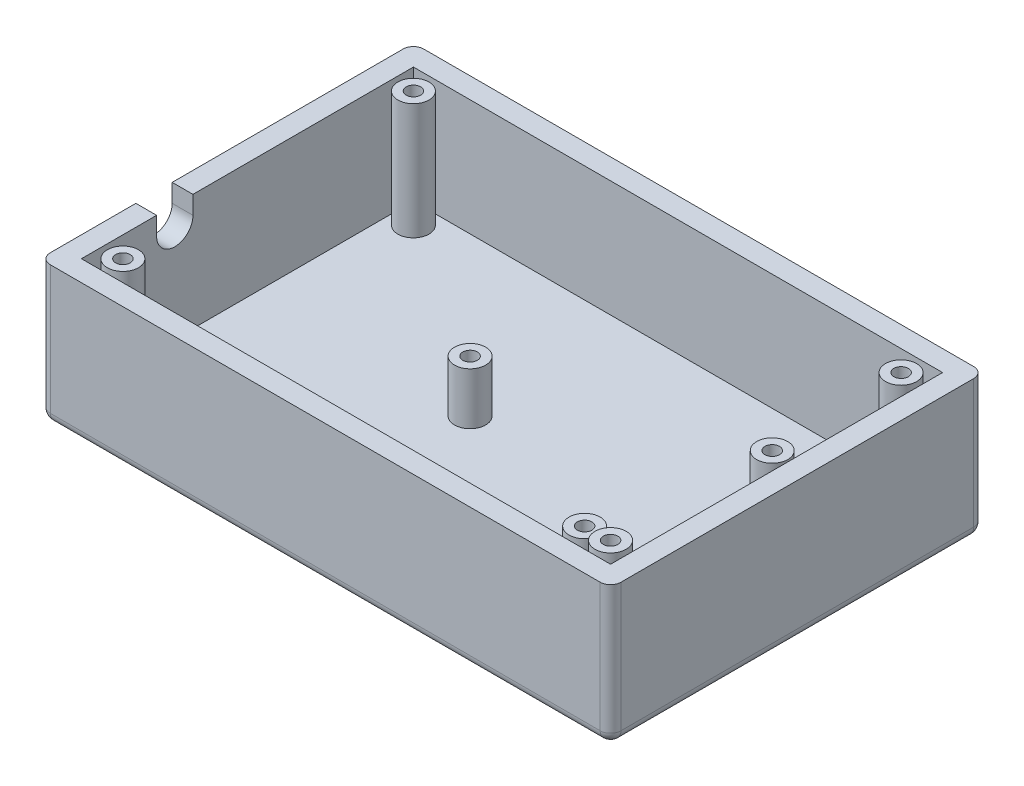
SolidWorks part; units mm, degrees
ref_plane "Front Plane" through (0, 0, 0) normal (0, 0, 1) x (1, 0, 0)
ref_plane "Top Plane" through (0, 0, 0) normal (0, 1, 0) x (1, 0, 0)
ref_plane "Right Plane" through (0, 0, 0) normal (1, 0, 0) x (0, 0, -1)
sketch "Sketch2" plane through (0, 0, 0) normal (0, 1, 0) x (1, 0, 0)
  line L1 (0, 0) -> (69.85, 0)
  line L2 (0, 0) -> (0, 45.72)
  line L3 (0, 45.72) -> (69.85, 45.72)
  line L4 (69.85, 0) -> (69.85, 45.72)
  dimension "D1" = 45.72
  dimension "D2" = 69.85
extrude "Boss-Extrude1" add sketch "Sketch2" along normal blind 17.018
sketch "Sketch3" plane through (0, 17.018, 0) normal (0, 1, 0) x (1, 0, 0)
  line L1 (2.54, 43.18) -> (67.31, 43.18)
  line L2 (2.54, 43.18) -> (2.54, 2.54)
  line L3 (2.54, 2.54) -> (67.31, 2.54)
  line L4 (67.31, 43.18) -> (67.31, 2.54)
  line L5 (0, 45.72) -> (0, 0) construction
  line L6 (69.85, 45.72) -> (0, 45.72) construction
  line L7 (69.85, 0) -> (69.85, 45.72) construction
  line L8 (0, 0) -> (69.85, 0) construction
  dimension "D1" = 2.54
  dimension "D2" = 2.54
  dimension "D3" = 2.54
  dimension "D4" = 2.54
  dimension "D5" = 40.64
extrude "Cut-Extrude1" cut sketch "Sketch3" against normal blind 14.224
sketch "Sketch9" plane through (0, 2.794, 0) normal (0, 1, 0) x (1, 0, 0)
  line L0 (67.31, 43.18) -> (67.31, 35.56)
  line L1 (67.31, 2.54) -> (67.31, 43.18) construction
  line L2 (67.31, 43.18) -> (66.675, 43.18)
  line L3 (67.31, 43.18) -> (2.54, 43.18) construction
  line L4 (66.675, 43.18) -> (66.675, 35.56)
  line L5 (66.675, 35.56) -> (67.31, 35.56)
  dimension "D1" = 7.62
  dimension "D2" = 0.635
sketch "Sketch13" plane through (0, 2.794, 0) normal (0, 1, 0) x (1, 0, 0)
  circle A0 centre (57.277, 32.3596) radius 1.905
  circle A1 centre (53.7972, 12.8778) radius 1.905
  circle A2 centre (28.7782, 23.876) radius 1.905
  dimension "D1" = 3.81
  dimension "D2" = 3.81
  dimension "D3" = 3.81
  dimension "D4" = 3.2004
  dimension "D5" = 9.398
  dimension "D6" = 19.4818
  dimension "D7" = 3.4798
  dimension "D8" = 8.4836
  dimension "D9" = 28.4988
extrude "Boss-Extrude5" add sketch "Sketch13" along normal blind 6.35
sketch "Sketch14" plane through (0, 9.144, 0) normal (0, 1, 0) x (1, 0, 0)
  circle A0 centre (57.277, 32.3596) radius 0.889
  circle A1 centre (53.7972, 12.8778) radius 0.889
  circle A2 centre (28.7782, 23.876) radius 0.889
  dimension "D2" = 1.778
extrude "Cut-Extrude4" cut sketch "Sketch14" against normal up to surface (6.35 mm away) up to face at (28.7782, 2.794, -21.971)
sketch "Sketch17" plane through (0, 0, 0) normal (-1, 0, 0) x (0, 0, 1)
  line L0 (-45.72, 17.018) -> (0, 17.018) construction
  line L1 (-45.72, 17.018) -> (-45.72, 0) construction
  line L2 (-16.1925, 14.7955) -> (-16.1925, 17.018)
  line L3 (-11.7475, 14.7955) -> (-11.7475, 17.018)
  line L4 (-11.7475, 17.018) -> (-16.1925, 17.018)
  arc A0 (-16.1925, 14.7955) -> (-11.7475, 14.7955) centre (-13.97, 14.7955) ccw
  dimension "D1" = 4.445
  dimension "D2" = 31.75
extrude "Cut-Extrude5" cut sketch "Sketch17" against normal up to surface (2.54 mm away) up to face at (2.54, 9.906, -22.86)
fillet "Fillet1" radius 1.27 8 edges at (34.925, 0, 0) (69.85, 0, -22.86) (34.925, 0, -45.72) (0, 0, -22.86) (0, 8.509, -45.72) (0, 8.509, 0) (69.85, 8.509, -45.72) (69.85, 8.509, 0)
sketch "Sketch18" plane through (0, 2.794, 0) normal (0, 1, 0) x (1, 0, 0)
  line L0 (2.54, 43.18) -> (2.54, 16.1925) construction
  line L1 (67.31, 2.54) -> (67.31, 43.18) construction
  line L5 (67.31, 43.18) -> (2.54, 43.18) construction
  line L7 (2.54, 2.54) -> (67.31, 2.54) construction
  line L8 (2.54, 2.54) -> (67.31, 2.54) construction
  line L9 (2.54, 43.18) -> (2.54, 2.54) construction
  line L10 (67.31, 43.18) -> (2.54, 43.18) construction
  line L11 (67.31, 2.54) -> (67.31, 43.18) construction
  circle A0 centre (5.08, 40.64) radius 1.905
  circle A1 centre (64.77, 40.64) radius 1.905
  circle A2 centre (5.08, 5.08) radius 1.905
  circle A3 centre (64.77, 5.08) radius 1.905
  dimension "D1" = 3.81
  dimension "D2" = 3.81
  dimension "D3" = 3.81
  dimension "D4" = 3.81
  dimension "D5" = 2.54
  dimension "D6" = 2.54
  dimension "D7" = 2.54
  dimension "D8" = 2.54
  dimension "D9" = 2.54
  dimension "D10" = 2.54
  dimension "D11" = 2.54
  dimension "D12" = 2.54
extrude "Boss-Extrude11" add sketch "Sketch18" along normal up to surface (14.224 mm away) up to face at (26.5113, 17.018, -20.6375)
sketch "Sketch19" plane through (0, 17.018, 0) normal (0, 1, 0) x (1, 0, 0)
  circle A0 centre (5.08, 40.64) radius 0.889
  circle A1 centre (64.77, 40.64) radius 0.889
  circle A2 centre (64.77, 5.08) radius 0.889
  circle A3 centre (5.08, 5.08) radius 0.889
  dimension "D4" = 1.778
extrude "Cut-Extrude6" cut sketch "Sketch19" against normal blind 6.35
sketch "Switch And LED pos" plane through (0, 2.794, 0) normal (0, 1, 0) x (1, 0, 0)
  line L0 (57.277, 32.3596) -> (23.7998, 32.3596)
  line L1 (23.7998, 32.3596) -> (23.7998, 17.78)
  line L2 (57.277, 32.3596) -> (62.7634, 32.3596)
  line L3 (62.7634, 32.3596) -> (62.7634, 14.6558)
  dimension "D1" = 33.4772
  dimension "D2" = 14.5796
  dimension "D3" = 5.4864
  dimension "D4" = 17.7038
